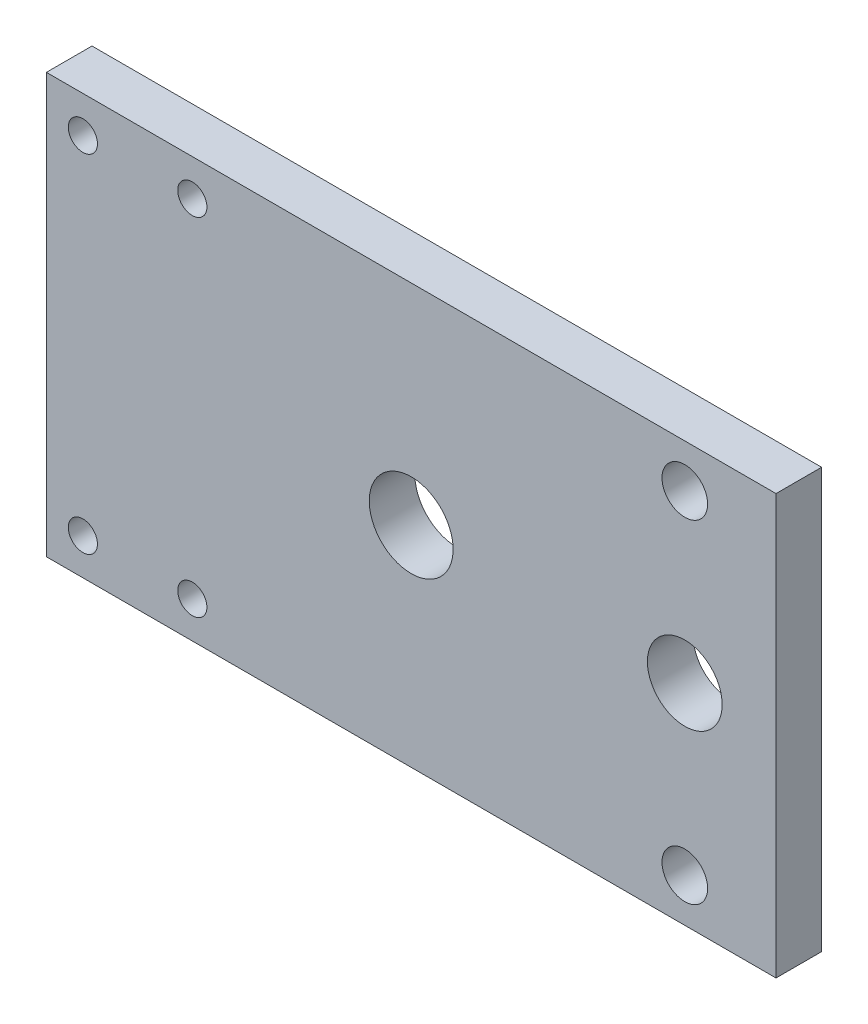
SolidWorks part; units mm, degrees
ref_plane "Front Plane" through (0, 0, 0) normal (0, 0, 1) x (1, 0, 0)
ref_plane "Top Plane" through (0, 0, 0) normal (0, 1, 0) x (1, 0, 0)
ref_plane "Right Plane" through (0, 0, 0) normal (1, 0, 0) x (0, 0, -1)
sketch "Sketch1" plane through (0, 0, 0) normal (0, 0, 1) x (1, 0, 0)
  line L0 (-25.3491, 0) -> (24.7222, 0) construction
  line L1 (40, -23) -> (-40, -23)
  line L2 (40, -23) -> (40, 23)
  line L3 (40, 23) -> (-40, 23)
  line L4 (-40, -23) -> (-40, 23)
  line L5 (40, -23) -> (-40, 23) construction
  line L6 (40, 23) -> (-40, -23) construction
  line L7 (30, 0) -> (30, 18.25)
  circle A0 centre (0, 0) radius 4.6
  circle A1 centre (30, 0) radius 4.1
  circle A2 centre (30, 18.25) radius 2.5
  circle A3 centre (30, -18.25) radius 2.5
  point P0 (0, 0)
  dimension "D1" = 9.2
  dimension "D2" = 8.2
  dimension "D7" = 5
  dimension "D3" = 46
  dimension "D4" = 30
  dimension "D5" = 80
  dimension "D6" = 18.25
extrude "Boss-Extrude1" add sketch "Sketch1" along normal blind 5 contours L4 L1 L2 L3 A0 A2 A1 A3 region at (0, -22.0772, 0)
sketch "Sketch2" plane through (0, 0, 5) normal (0, 0, 1) x (1, 0, 0)
  line L0 (-40, -23) -> (-40, 23)
  line L1 (-40, -23) -> (-20, -23)
  line L2 (-40, 23) -> (-20, 23)
  line L3 (-20, -23) -> (-20, 23)
  line L4 (-40, 23) -> (-40, -23)
  line L5 (-40, -23) -> (40, -23)
  line L6 (40, -23) -> (40, 23)
  line L7 (40, 23) -> (-40, 23)
  line L8 (-40, 23) -> (-40, -23)
  line L9 (-40, -23) -> (40, -23)
  line L10 (40, -23) -> (40, 23)
  line L11 (40, 23) -> (-40, 23)
  line L12 (-40, -19) -> (-24, -19)
  line L13 (-24, -19) -> (-24, 19)
  line L14 (-40, 19) -> (-24, 19)
  line L15 (-36, -23) -> (-36, 23)
  circle A0 centre (-36, 19) radius 1.6
  circle A1 centre (-24, 19) radius 1.6
  circle A2 centre (-24, -19) radius 1.6
  circle A3 centre (-36, -19) radius 1.6
  dimension "D5" = 3.2
  dimension "D6" = 3.2
  dimension "D7" = 3.2
  dimension "D8" = 3.2
  dimension "D2" = 20
  dimension "D1" = 0
  dimension "D3" = 4
  dimension "D4" = 4
extrude "Cut-Extrude1" cut sketch "Sketch2" against normal blind 10 contours L15 A0 L14 | L15 A0 L14 | L14 A0 L15 | L14 A0 L15 | L13 A1 L14 | L14 A1 L13 | L12 A3 L15 | L15 A3 L12 | L12 A3 L15 | L15 A3 L12 | L12 A2 L13 | L13 A2 L12 region at (-36.6791, -18.3209, 5) region at (-36.6791, -19.6791, 5) region at (-35.3209, -19.6791, 5) region at (-36.6791, 19.6791, 5) region at (-36.6791, 18.3209, 5) region at (-35.3209, -18.3209, 5) region at (-35.3209, 19.6791, 5) region at (-35.3209, 18.3209, 5) region at (-24.6791, -18.3209, 5) region at (-23.7736, -19.2264, 5) region at (-23.7736, 19.2264, 5) region at (-24.6791, 18.3209, 5)
